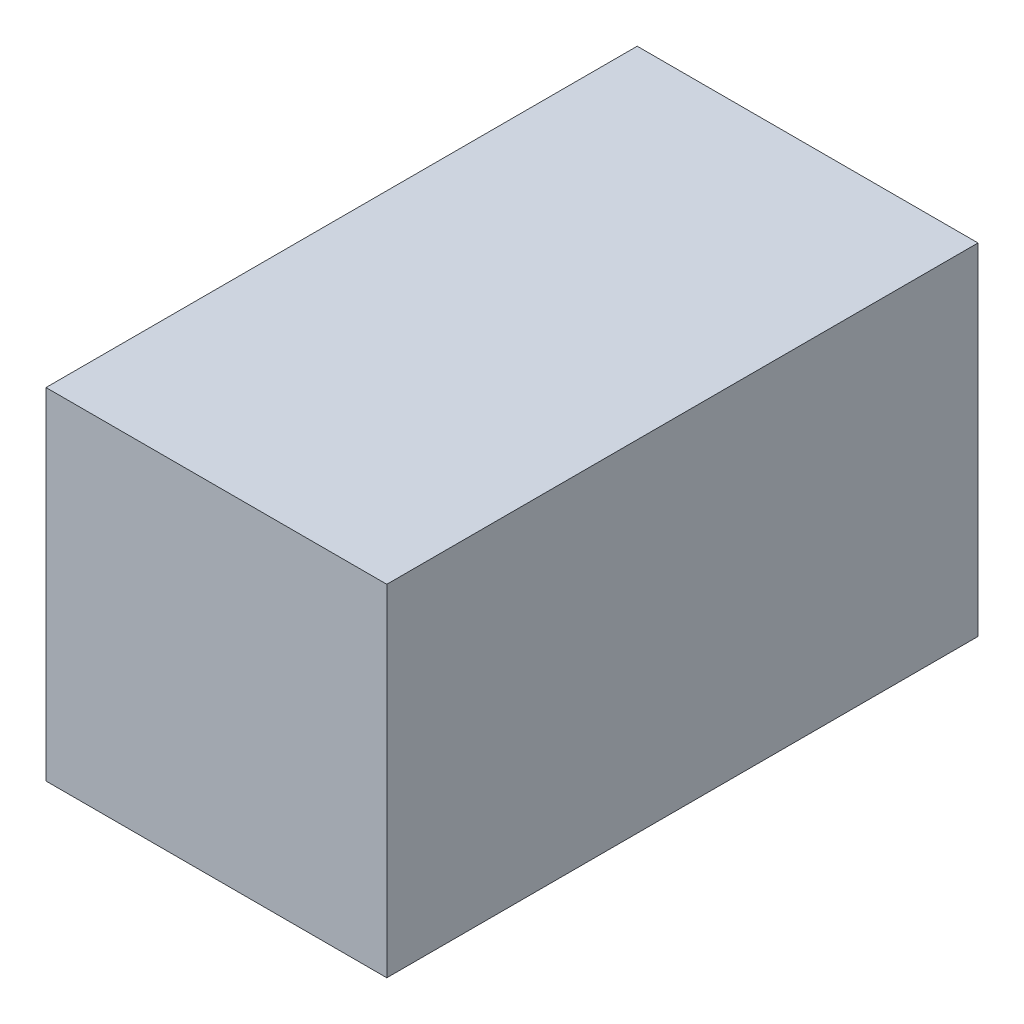
SolidWorks part; units mm, degrees
ref_plane "Front Plane" through (0, 0, 0) normal (0, 0, 1) x (1, 0, 0)
ref_plane "Top Plane" through (0, 0, 0) normal (0, 1, 0) x (1, 0, 0)
ref_plane "Right Plane" through (0, 0, 0) normal (1, 0, 0) x (0, 0, -1)
other "Center of Mass"
sketch "Sketch2" plane through (0, 0, 0) normal (1, 0, 0) x (0, 0, -1)
  line L1 (0, 0) -> (42.5, 0)
  line L2 (0, 0) -> (0, 24.5)
  line L3 (0, 24.5) -> (42.5, 24.5)
  line L4 (42.5, 0) -> (42.5, 24.5)
  dimension "D1" = 42.5
  dimension "D2" = 24.5
extrude "Boss-Extrude1" add sketch "Sketch2" along normal blind 12.25 and the other way blind 12.25
